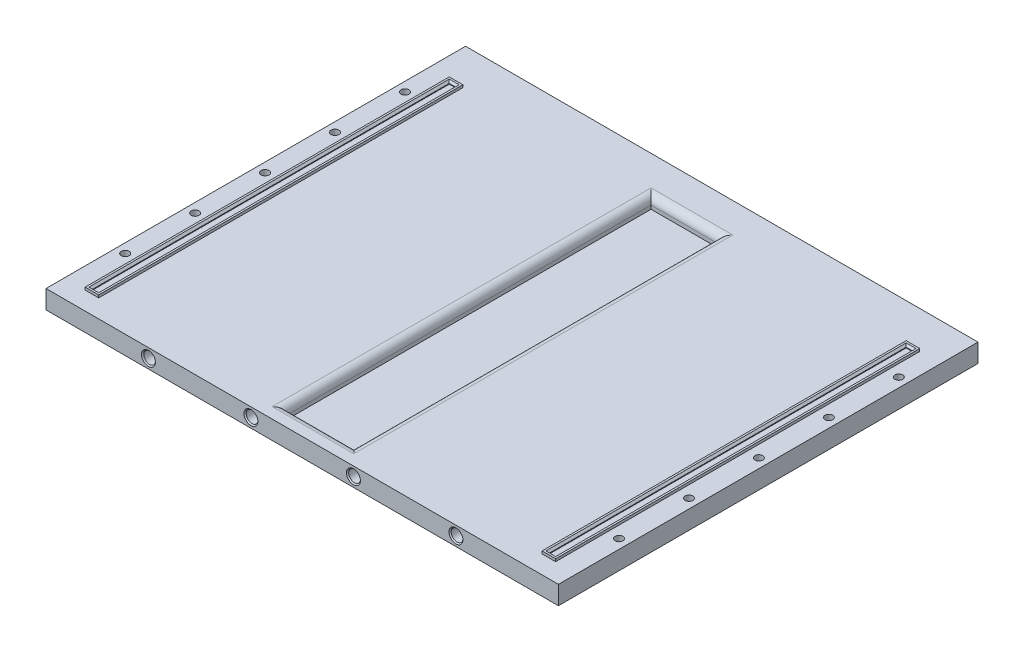
SolidWorks part; units mm, degrees
ref_plane "Спереди" through (0, 0, 0) normal (0, 0, 1) x (1, 0, 0)
ref_plane "Сверху" through (0, 0, 0) normal (0, 1, 0) x (1, 0, 0)
ref_plane "Справа" through (0, 0, 0) normal (1, 0, 0) x (0, 0, -1)
sketch "Эскиз1" plane through (0, 0, 0) normal (0, 1, 0) x (1, 0, 0)
  line L5 (-69, -56.5) -> (69, -56.5)
  line L6 (-69, -56.5) -> (-69, 56.5)
  line L7 (-69, 56.5) -> (69, 56.5)
  line L8 (69, -56.5) -> (69, 56.5)
  line L9 (-69, -56.5) -> (69, 56.5) construction
  line L10 (-69, 56.5) -> (69, -56.5) construction
  point P0 (0, 0)
  dimension "D1" = 113
  dimension "D2" = 138
extrude "Основание" add sketch "Эскиз1" along normal blind 5
sketch "Эскиз6" plane through (0, 0, 0) normal (0, -1, 0) x (1, 0, 0)
  line L0 (0, 45.5668) -> (0, -26.923) construction
  line L1 (-15.8226, 0) -> (3.0664, 0) construction
  line L2 (-37, 37) -> (0, 37) construction
  line L3 (-47, 47) -> (-27, 47)
  line L4 (-47, 47) -> (-47, 27)
  line L5 (-47, 27) -> (-27, 27)
  line L6 (-27, 47) -> (-27, 27)
  line L7 (-47, 47) -> (-27, 27) construction
  line L8 (-47, 27) -> (-27, 47) construction
  line L9 (-37, 37) -> (-37, 0) construction
  line L10 (47, 47) -> (27, 47)
  line L11 (47, 47) -> (47, 27)
  line L12 (47, 27) -> (27, 27)
  line L13 (27, 47) -> (27, 27)
  line L14 (27, -47) -> (27, -27)
  line L15 (47, -27) -> (27, -27)
  line L16 (47, -47) -> (47, -27)
  line L17 (47, -47) -> (27, -47)
  line L18 (-47, -47) -> (-27, -47)
  line L19 (-47, -47) -> (-47, -27)
  line L20 (-47, -27) -> (-27, -27)
  line L21 (-27, -47) -> (-27, -27)
  point P1 (-37, 37)
  dimension "D1" = 20
  dimension "D2" = 37
extrude "Ножки" add sketch "Эскиз6" along normal blind 4
fillet "Скругление ножек" radius 2 16 edges at (-37, -4, 27) (-47, -4, 37) (-37, -4, 47) (-27, -4, 37) (-37, -4, -27) (-27, -4, -37) (-37, -4, -47) (-47, -4, -37) (27, -4, -37) (37, -4, -27) (47, -4, -37) (37, -4, -47) (37, -4, 27) (27, -4, 37) (37, -4, 47) (47, -4, 37)
fillet "Скругление3" radius 2 48 edges at (46.4142, -3.4142, 27.5858) (27.5858, -3.4142, 27.5858) (46.4142, -3.4142, 46.4142) (27.5858, -3.4142, 46.4142) (-46.4142, -3.4142, 46.4142) (27.5858, -3.4142, -27.5858) (-46.4142, -3.4142, 27.5858) (-27.5858, -3.4142, 27.5858) (-27.5858, -3.4142, 46.4142) (27.5858, -3.4142, -46.4142) (46.4142, -3.4142, -46.4142) (46.4142, -3.4142, -27.5858) (-27.5858, -3.4142, -46.4142) (-46.4142, -3.4142, -46.4142) (-27.5858, -3.4142, -27.5858) (-46.4142, -3.4142, -27.5858) (37, 0, 27) (47, 0, 37) (47, -1, 27) (27, 0, 37) (27, -1, 27) (37, 0, 47) (47, -1, 47) (27, -1, 47) (-47, 0, 37) (-37, 0, 47) (-47, -1, 47) (27, 0, -37) (37, 0, -27) (27, -1, -27) (-37, 0, 27) (-47, -1, 27) (-27, 0, 37) (-27, -1, 27) (-27, -1, 47) (37, 0, -47) (27, -1, -47) (47, 0, -37) (47, -1, -47) (47, -1, -27) (-37, 0, -47) (-27, 0, -37) (-27, -1, -47) (-47, 0, -37) (-47, -1, -47) (-37, 0, -27) (-27, -1, -27) (-47, -1, -27)
sketch "Эскиз2" plane through (0, 5, 0) normal (0, 1, 0) x (1, 0, 0)
  line L0 (0, 0) -> (0, -25.5598) construction
  line L1 (-61.525, 37.0772) -> (-61.525, 5.6487) construction
  line L2 (-21.6597, -2.575) -> (12.5108, -2.575) construction
  line L3 (-59.7, 46.45) -> (-63.35, 46.45)
  line L4 (-63.35, 46.45) -> (-63.35, -51.6)
  line L5 (-63.35, -2.575) -> (-62.35, -2.575)
  line L6 (-62.35, -50.6) -> (-62.35, 45.45)
  line L7 (-62.35, 45.45) -> (-60.7, 45.45)
  line L8 (-61.525, 45.45) -> (-61.525, 46.45)
  line L9 (-60.7, -50.6) -> (-60.7, 45.45)
  line L10 (-59.7, -2.575) -> (-60.7, -2.575)
  line L11 (-59.7, 46.45) -> (-59.7, -51.6)
  line L12 (-62.35, -50.6) -> (-60.7, -50.6)
  line L13 (-59.7, -51.6) -> (-63.35, -51.6)
  line L14 (-61.525, -50.6) -> (-61.525, -51.6)
  line L15 (61.525, -50.6) -> (61.525, -51.6)
  line L16 (59.7, -51.6) -> (63.35, -51.6)
  line L17 (62.35, -50.6) -> (60.7, -50.6)
  line L18 (59.7, 46.45) -> (59.7, -51.6)
  line L19 (59.7, -2.575) -> (60.7, -2.575)
  line L20 (60.7, -50.6) -> (60.7, 45.45)
  line L21 (61.525, 45.45) -> (61.525, 46.45)
  line L22 (62.35, 45.45) -> (60.7, 45.45)
  line L23 (62.35, -50.6) -> (62.35, 45.45)
  line L24 (63.35, -2.575) -> (62.35, -2.575)
  line L25 (63.35, 46.45) -> (63.35, -51.6)
  line L26 (59.7, 46.45) -> (63.35, 46.45)
  line L27 (-69, -56.5) -> (69, -56.5) construction
  dimension "D1" = 1
  dimension "D2" = 96.05
  dimension "D3" = 1.65
  dimension "D4" = 121.4
  dimension "D5" = 5.9
extrude "Ложемент материнской платы" add sketch "Эскиз2" along normal blind 0.7 contours L14 L12 L6 L5 L4 L13 | L7 L8 L3 L4 L5 L6 | L11 L3 L8 L7 L9 L10 | L12 L14 L13 L11 L10 L9 | L26 L21 L22 L23 L24 L25 | L26 L18 L19 L20 L22 L21 | L17 L20 L19 L18 L16 L15 | L25 L24 L23 L17 L15 L16 region at (-60.2151, 5, -22.3349) region at (-62.8349, 5, -22.3349) region at (-60.2151, 5, 27.4849) region at (-62.8349, 5, 27.4849) region at (62.8349, 5, 27.4849) region at (60.2151, 5, 27.4849) region at (62.8349, 5, -22.3349) region at (60.2151, 5, -22.3349)
fillet "Фаска первого ложемента" radius 0.5 4 edges at (-61.525, 5.7, -45.45) (-60.7, 5.7, 2.575) (-61.525, 5.7, 50.6) (-62.35, 5.7, 2.575) type face fillet profile chamfer first side face at (-61.525, 5.35, -45.45) first side face at (-61.525, 5.35, 50.6) first side face at (-60.7, 5.35, 2.575) first side face at (-62.35, 5.35, 2.575) second side face at (-61.525, 5.7, 2.575)
fillet "Фаска второго ложемента" radius 0.5 4 edges at (61.525, 5.7, 50.6) (60.7, 5.7, 2.575) (61.525, 5.7, -45.45) (62.35, 5.7, 2.575) type face fillet profile chamfer first side face at (61.525, 5.35, -45.45) first side face at (62.35, 5.35, 2.575) first side face at (60.7, 5.35, 2.575) first side face at (61.525, 5.35, 50.6) second side face at (61.525, 5.7, 2.575)
sketch "Эскиз3" plane through (0, 0, -56.5) normal (0, 0, -1) x (-1, 0, 0)
  line L0 (-69, 0) -> (69, 0) construction
  line L1 (-69, 5) -> (-69, 0) construction
  line L2 (-41.4, 2.5) -> (-69, 2.5) construction
  line L3 (41.4, 2.5) -> (69, 2.5) construction
  line L6 (69, 5) -> (69, 0) construction
  line L7 (-41.4, 2.5) -> (-13.8, 2.5) construction
  line L8 (-13.8, 2.5) -> (13.8, 2.5) construction
  line L9 (13.8, 2.5) -> (41.4, 2.5) construction
  circle A0 centre (-41.4, 2.5) radius 1.575
  circle A1 centre (-13.8, 2.5) radius 1.575
  circle A2 centre (13.8, 2.5) radius 1.575
  circle A3 centre (41.4, 2.5) radius 1.575
  dimension "D4" = 3.15
  dimension "D1" = 2.5
  dimension "D5" = 27.6
  dimension "D3" = 4
extrude "Крепежные отверсия передней и задней стенки" cut sketch "Эскиз3" against normal blind 4.2
ref_plane "Плоскость1" through (0, 0, 0) normal (0, 0, -1) x (-1, 0, 0)
mirror "Зеркальное отражение1" about plane through (0, 0, 0) normal (0, 0, -1) of "Крепежные отверсия передней и задней стенки"
chamfer "Фаска под запресовку" distance 0.3 angle 45 8 edges at (39.825, 2.5, -56.5) (-42.975, 2.5, -56.5) (-15.375, 2.5, -56.5) (12.225, 2.5, -56.5) (39.825, 2.5, 56.5) (12.225, 2.5, 56.5) (-15.375, 2.5, 56.5) (-42.975, 2.5, 56.5)
sketch "Эскиз4" plane through (0, 0, 0) normal (0, -1, 0) x (1, 0, 0)
  line L0 (0, 34.8353) -> (0, -23.754) construction
  line L1 (-66.5, 56.5) -> (-66.5, 37.6667) construction
  line L2 (-69, 56.5) -> (69, 56.5) construction
  line L3 (-66.5, 37.6667) -> (-66.5, 18.8333) construction
  line L4 (-66.5, 18.8333) -> (-66.5, 0) construction
  line L5 (-66.5, 0) -> (-66.5, -18.8333) construction
  line L6 (-66.5, -18.8333) -> (-66.5, -37.6667) construction
  line L7 (-66.5, -37.6667) -> (-66.5, -56.5) construction
  line L8 (69, -56.5) -> (-69, -56.5) construction
  line L9 (-69, -56.5) -> (-69, 56.5) construction
  circle A0 centre (-66.5, 37.6667) radius 1.05
  circle A1 centre (-66.5, 18.8333) radius 1.05
  circle A2 centre (-66.5, 0) radius 1.05
  circle A3 centre (-66.5, -18.8333) radius 1.05
  circle A4 centre (-66.5, -37.6667) radius 1.05
  circle A5 centre (66.5, -37.6667) radius 1.05
  circle A6 centre (66.5, -18.8333) radius 1.05
  circle A7 centre (66.5, 0) radius 1.05
  circle A8 centre (66.5, 18.8333) radius 1.05
  circle A9 centre (66.5, 37.6667) radius 1.05
  dimension "D3" = 2.1
  dimension "D2" = 2.5
  dimension "D1" = 5
extrude "Отверстия крепежных винтов" cut sketch "Эскиз4" against normal up to next
sketch "Эскиз5" plane through (0, 0, 0) normal (0, -1, 0) x (1, 0, 0)
  line L0 (0, 88.0608) -> (0, 29.4715) construction
  line L1 (-66.5, 56.5) -> (-66.5, 37.6667) construction
  line L2 (-66.5, 37.6667) -> (-66.5, 18.8333) construction
  line L3 (-66.5, 18.8333) -> (-66.5, 0) construction
  line L4 (-66.5, 0) -> (-66.5, -18.8333) construction
  line L5 (-66.5, -18.8333) -> (-66.5, -37.6667) construction
  line L6 (-66.5, -37.6667) -> (-66.5, -56.5) construction
  line L7 (69, -56.5) -> (-69, -56.5) construction
  line L8 (-69, 56.5) -> (69, 56.5) construction
  circle A0 centre (-66.5, 37.6667) radius 2
  circle A1 centre (-66.5, 18.8333) radius 2
  circle A2 centre (-66.5, 0) radius 2
  circle A3 centre (-66.5, -18.8333) radius 2
  circle A4 centre (-66.5, -37.6667) radius 2
  circle A5 centre (66.5, -37.6667) radius 2
  circle A6 centre (66.5, -18.8333) radius 2
  circle A7 centre (66.5, 0) radius 2
  circle A8 centre (66.5, 18.8333) radius 2
  circle A9 centre (66.5, 37.6667) radius 2
  circle A10 centre (-66.5, -37.6667) radius 1.05 construction
  dimension "D1" = 4
extrude "Потай головок винтов" cut sketch "Эскиз5" against normal blind 3
sketch "Эскиз8" plane through (0, 5, 0) normal (0, 1, 0) x (1, 0, 0)
  line L0 (-59.7, 46.45) -> (-38.3699, 46.45) construction
  line L1 (-59.7, -51.6) -> (-44.5392, -51.6) construction
  line L2 (-59.7, -51.6) -> (-63.35, -51.6) construction
  line L3 (-59.7, 46.45) -> (-63.35, 46.45) construction
  line L4 (0, 67.288) -> (0, -49932.712) construction
  line L5 (-9, 46.45) -> (9, 46.45)
  line L6 (-9, 46.45) -> (-9, -51.6)
  line L7 (-9, -51.6) -> (9, -51.6)
  line L8 (9, 46.45) -> (9, -51.6)
  point P16 (0, 46.45)
  dimension "D1" = 18
extrude "Ложемент для кабелей" cut sketch "Эскиз8" against normal blind 3
fillet "Скругление ложемента кабелей" radius 2 4 edges at (-9, 5, 2.575) (0, 5, -46.45) (9, 5, 2.575) (0, 5, 51.6)
